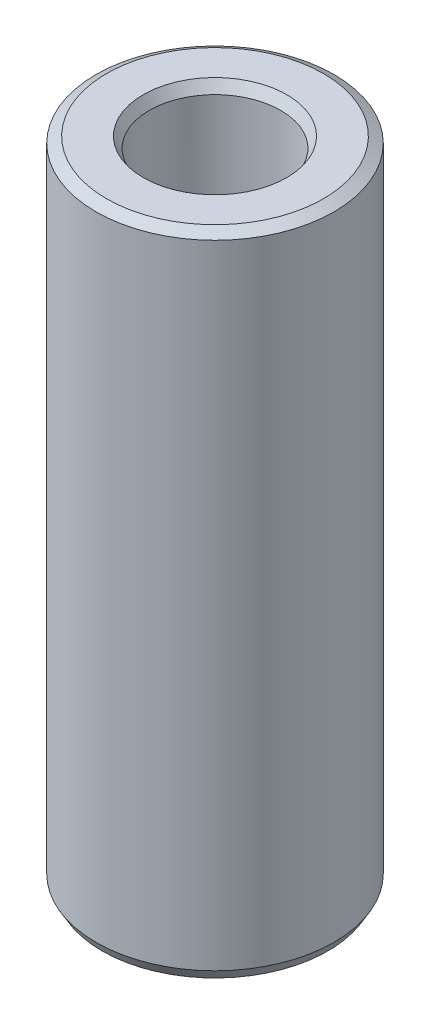
SolidWorks part; units mm, degrees
ref_plane "Front Plane" through (0, 0, 0) normal (0, 0, 1) x (1, 0, 0)
ref_plane "Top Plane" through (0, 0, 0) normal (0, 1, 0) x (1, 0, 0)
ref_plane "Right Plane" through (0, 0, 0) normal (1, 0, 0) x (0, 0, -1)
sketch "Sketch1" plane through (0, 0, 0) normal (0, 1, 0) x (1, 0, 0)
  circle A0 centre (0, 0) radius 42.5
  dimension "SLEEVE_OD" = 85
extrude "Boss-Extrude1" add sketch "Sketch1" along normal blind 231.8751
sketch "Sketch2" plane through (0, 0, 0) normal (0, 1, 0) x (1, 0, 0)
  circle A0 centre (0, 0) radius 23.48
  dimension "BORE_D" = 46.96
extrude "Cut-Extrude1" cut sketch "Sketch2" along normal through all
chamfer "Chamfer1" distance 2.1706 angle 60 4 edges at (0, 231.8751, 23.48) (0, 0, 23.48) (0, 0, 42.5) (0, 231.8751, 42.5) first distance on face at (0, 231.8751, 23.48) first distance on face at (0, 0, 23.48) first distance on face at (0, 231.8751, 42.5)
